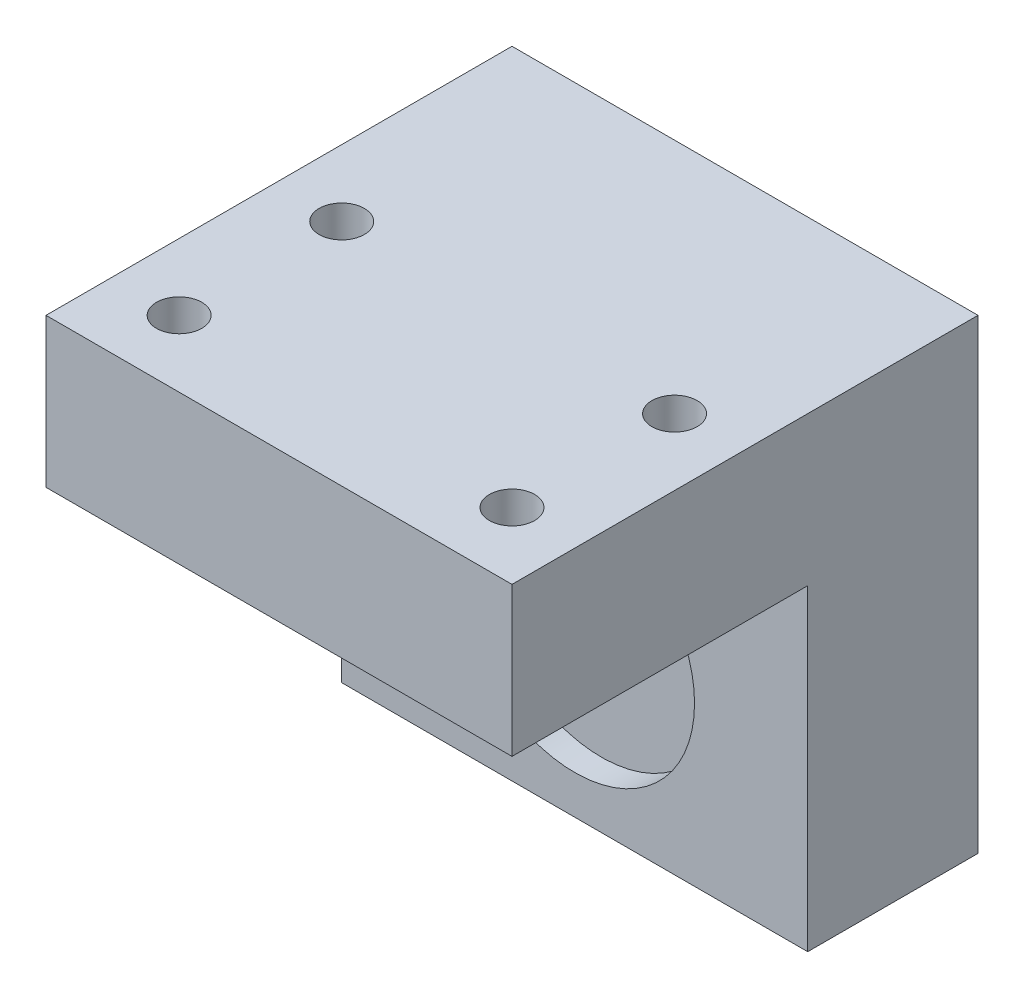
SolidWorks part; units mm, degrees
ref_plane "Front Plane" through (0, 0, 0) normal (1, 0, 0) x (0, 1, 0)
ref_plane "Top Plane" through (0, 0, 0) normal (0, 0, 1) x (0, 1, 0)
ref_plane "Right Plane" through (0, 0, 0) normal (0, 1, 0) x (-1, 0, 0)
sketch "Sketch1" plane through (0, 0, 0) normal (1, 0, 0) x (0, 1, 0)
  line L0 (0, -12.79) -> (35, -12.79)
  line L9 (35, -12.79) -> (35, 22.21)
  line L10 (35, 22.21) -> (23.81, 22.21)
  line L11 (23.81, 22.21) -> (23.81, 0)
  line L12 (23.81, 0) -> (0, 0)
  line L13 (0, 0) -> (0, -12.79)
  point P4 (0, 0)
  point P8 (0, 0)
  point P9 (0, 0)
  dimension "D1" = 35
  dimension "D2" = 35
  dimension "D3" = 12.79
  dimension "D4" = 11.19
extrude "Boss-Extrude1" add sketch "Sketch1" along normal blind 35 contours L11 L12 L13 L0 L9 L10
sketch "Sketch2" plane through (0, 0, 0) normal (0, 0, 1) x (1, 0, 0)
  line L0 (35, 23.81) -> (35, 0) construction
  line L3 (35, 0) -> (0, 0) construction
  circle A0 centre (17.5, 11.905) radius 3
  circle A1 centre (17.5, 11.905) radius 9
  point P6 (0, 0)
  dimension "D4" = 6
  dimension "D5" = 18
  dimension "D1" = 17.5
  dimension "D2" = 11.905
extrude "Cut-Extrude1" cut sketch "Sketch2" against normal up to next contours A0
extrude "Cut-Extrude2" cut sketch "Sketch2<4>" against normal blind 2 contours A1
sketch "Sketch2<4>" plane through (0, 0, 0) normal (0, 0, 1) x (1, 0, 0) same geometry as "Sketch2"
sketch "Sketch5" plane through (0, 23.81, 0) normal (0, -1, 0) x (1, 0, 0)
  line L0 (0, 22.21) -> (0, 0) construction
  line L1 (35, 22.21) -> (35, 0) construction
  line L2 (35, 22.21) -> (0, 22.21) construction
  line L3 (35, 0) -> (0, 0) construction
  circle A0 centre (5, 17.21) radius 1.7
  circle A1 centre (30, 17.21) radius 1.7
  circle A2 centre (30, 5) radius 1.7
  circle A3 centre (5, 5) radius 1.7
  point P12 (0, 0)
  point P13 (0, 0)
  point P14 (5.903, 7.4172)
  point P19 (5, 5)
  dimension "D1" = 3.4
  dimension "D4" = 5
  dimension "D2" = 5
  dimension "D3" = 5
  dimension "D5" = 5
extrude "Cut-Extrude3" cut sketch "Sketch5" against normal up to next
equation "\"P\"= 300'Load (N)"
equation "\"L1\"= 40'Length 1 (mm)"
equation "\"L2\"= 35'Length 2 (mm)"
equation "\"Sy\"= 60'Yield Strength (MPa)"
equation "\"SF\"= 3'Safety Factor"
equation "\"E\"= 3500'Mod. El. (MPa)"
equation "\"W\"= 35'Width (mm)"
equation "\"D\"= 0.30'Max Deflection (mm)"
equation "\"t1\"= ( ( 4 * \"P\" * \"L1\" ^ 3 ) / ( \"E\" * \"W\" * \"D\" ) ) ^ ( 1 / 3 )'Thickness 1 (mm)"
equation "\"t2\"= ( ( 4 * \"P\" * \"L2\" ^ 3 ) / ( \"E\" * \"W\" * \"D\" ) ) ^ ( 1 / 3 )'Thickness 2 (mm)"
